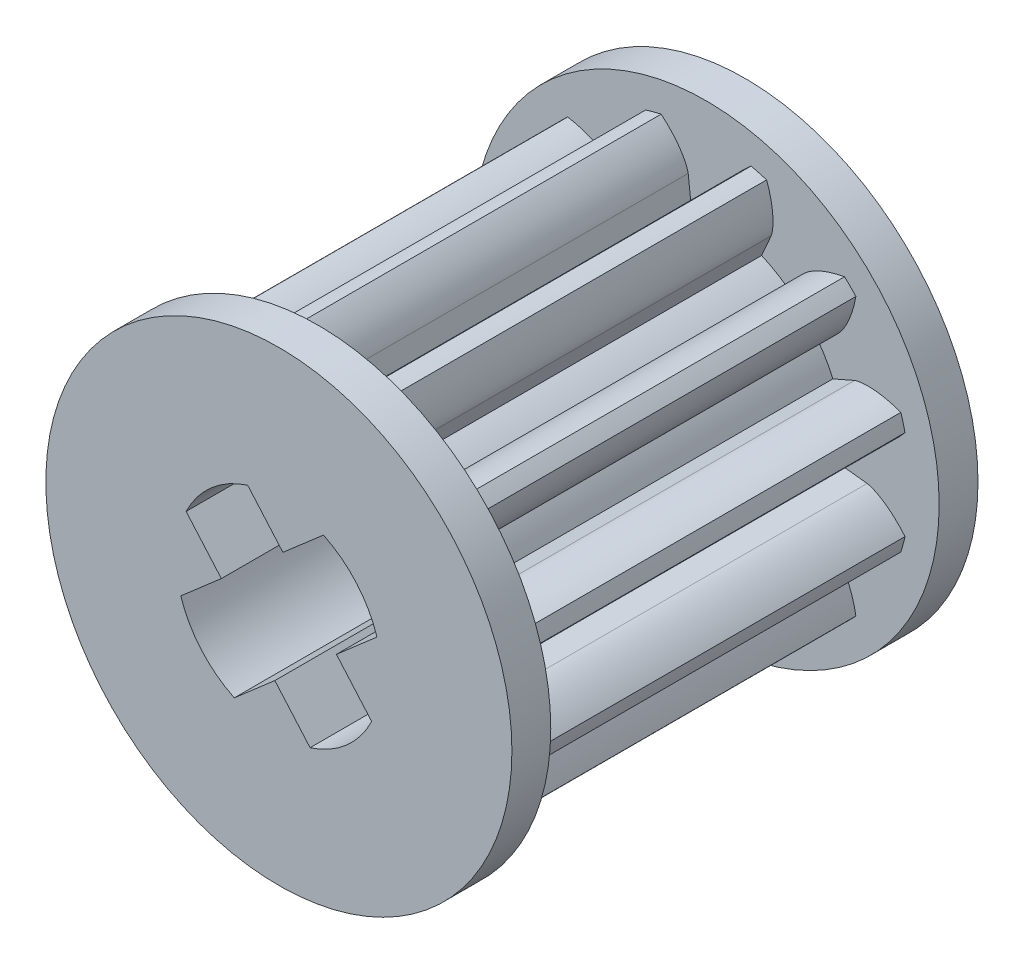
SolidWorks part; units mm, degrees
ref_plane "Front Plane" through (0, 0, 0) normal (0, 0, 1) x (1, 0, 0)
ref_plane "Top Plane" through (0, 0, 0) normal (0, 1, 0) x (1, 0, 0)
ref_plane "Right Plane" through (0, 0, 0) normal (1, 0, 0) x (0, 0, -1)
ref_axis "Axis1" [suppressed] through (0, 0, 71.2135) along (0, 0, -1)
sketch "Sketch1" plane through (0, 0, 0) normal (0, 0, 1) x (1, 0, 0)
  circle A0 centre (0, 0) radius 3.5625
  circle A1 centre (0, 0) radius 4.1723
  circle A2 centre (0, 0) radius 3.75
  circle A3 centre (0, 0) radius 4.5
  circle A4 centre (0, 0) radius 5.25
  dimension "Pitch" = 9
  dimension "Addendum" = 10.5
  dimension "Clearance" = 7.5
  dimension "Base" = 8.3447
  dimension "Root" = 7.125
extrude "Boss-Extrude1" add sketch "Sketch1" along normal blind 10 contours A4
sketch "Sketch3" plane through (0, 0, 0) normal (0, 0, 1) x (1, 0, 0)
  line L0 (0.4615, 4.1467) -> (0, 0) construction
  line L1 (0.7855, 4.0977) -> (0, 0) construction
  line L2 (1.1046, 4.0235) -> (0, 0) construction
  line L3 (1.4168, 3.9244) -> (0, 0) construction
  line L4 (1.7204, 3.8011) -> (0, 0) construction
  line L5 (2.0133, 3.6544) -> (0, 0) construction
  line L6 (2.2938, 3.4852) -> (0, 0) construction
  line L7 (2.5602, 3.2945) -> (0, 0) construction
  line L8 (2.8108, 3.0835) -> (0, 0) construction
  line L9 (3.044, 2.8534) -> (0, 0) construction
  line L10 (3.2585, 2.6058) -> (0, 0) construction
  line L11 (0.7855, 4.0977) -> (0.4636, 4.1594) construction
  line L12 (3.2585, 2.6058) -> (1.2119, 5.1651) construction
  line L13 (1.1046, 4.0235) -> (0.4725, 4.197) construction
  line L14 (1.4168, 3.9244) -> (0.4922, 4.2582) construction
  line L15 (1.7204, 3.8011) -> (0.5262, 4.3416) construction
  line L16 (2.0133, 3.6544) -> (0.5782, 4.4451) construction
  line L17 (2.2938, 3.4852) -> (0.6514, 4.5662) construction
  line L18 (2.5602, 3.2945) -> (0.7489, 4.702) construction
  line L19 (2.8108, 3.0835) -> (0.8734, 4.8495) construction
  line L20 (3.044, 2.8534) -> (1.0271, 5.0051) construction
  line L21 (0, 0) -> (0, 4.5) construction
  line L22 (0, 0) -> (0.5874, 4.4615)
  line L23 (0, 0) -> (-0.5874, 4.4615)
  line L24 (0.4615, 4.1467) -> (0.3941, 3.5406)
  line L25 (-0.4615, 4.1467) -> (-0.3941, 3.5406)
  circle A0 centre (0, 0) radius 4.1723 construction
  circle A1 centre (0, 0) radius 4.5 construction
  arc A2 (3.2585, 2.6058) -> (0.4615, 4.1467) centre (0, 0) ccw construction
  circle A3 centre (0, 0) radius 3.5625 construction
  circle A4 centre (0, 0) radius 3.5625
  circle A5 centre (0, 0) radius 5.25 construction
  circle A6 centre (0, 0) radius 5.25
  spline S0 degree 3 poles (0.4615, 4.1467) (0.464, 4.1637) (0.473, 4.2013) (0.4941, 4.2666) (0.5286, 4.35) (0.6061, 4.5031) (0.722, 4.6743) (0.9298, 4.9199) (1.0915, 5.0686) (1.2119, 5.1651) knots 0 0 0 0 0.040008 0.090018 0.16003 0.250047 0.489907 0.639935 1 1 1 1
  spline S1 degree 3 poles (-0.4615, 4.1467) (-0.464, 4.1637) (-0.473, 4.2013) (-0.4941, 4.2666) (-0.5286, 4.35) (-0.6061, 4.5031) (-0.722, 4.6743) (-0.9298, 4.9199) (-1.0915, 5.0686) (-1.2119, 5.1651) knots 0 0 0 0 0.040008 0.090018 0.16003 0.250047 0.489907 0.639935 1 1 1 1
  point P18 (0, 0)
  dimension "D2" = 45
  dimension "D3" = 0.3277
  dimension "D4" = 3.2769
  dimension "D5" = 0.6554
  dimension "D6" = 0.9831
  dimension "D7" = 1.3108
  dimension "D8" = 1.6385
  dimension "D9" = 1.9662
  dimension "D10" = 2.2939
  dimension "D11" = 2.6216
  dimension "D12" = 2.9492
  dimension "D13" = 15
  dimension "D1" = 11
extrude "Cut-Extrude3" cut sketch "Sketch3" along normal through all contours S1 L25 A4 L24 S0 A6 region at (0, 4.5519, 0)
fillet "Fillet2" [suppressed] radius 0.05
pattern_circular "CirPattern1" count 12 over 360 about axis through (0, 0, 71.2135) along (0, 0, -1) of "Cut-Extrude3", "Fillet2"
ref_plane "Plane2" through (0, 0, 5) normal (0, 0, 1) x (1, 0, 0)
sketch "Sketch6" plane through (0, 0, 10) normal (0, 0, 1) x (1, 0, 0)
  circle A0 centre (0, 0) radius 6
  dimension "D1" = 12
extrude "Boss-Extrude2" add sketch "Sketch6" along normal blind 1
mirror "Mirror1" about plane through (0, 0, 5) normal (0, 0, 1) of "Boss-Extrude2"
sketch "Sketch5" plane through (0, 0, 0) normal (0, 0, 1) x (1, 0, 0)
  line L0 (-0.8803, 2.2327) -> (0.0791, 1.1286) construction
  line L1 (-1.1286, 0.0791) -> (-2.088, 1.1833) construction
  line L2 (-2.2327, -0.8803) -> (-1.1286, 0.0791) construction
  line L3 (-0.0791, -1.1286) -> (-1.1833, -2.088) construction
  line L4 (0.8803, -2.2327) -> (-0.0791, -1.1286) construction
  line L5 (1.1286, -0.0791) -> (2.088, -1.1833) construction
  line L6 (2.2327, 0.8803) -> (1.1286, -0.0791) construction
  line L7 (0.0791, 1.1286) -> (1.1833, 2.088) construction
  line L8 (-0.8803, 2.2327) -> (0.0791, 1.1286)
  line L9 (-1.1286, 0.0791) -> (-2.088, 1.1833)
  line L10 (-2.2327, -0.8803) -> (-1.1286, 0.0791)
  line L11 (-0.0791, -1.1286) -> (-1.1833, -2.088)
  line L12 (0.8803, -2.2327) -> (-0.0791, -1.1286)
  line L13 (1.1286, -0.0791) -> (2.088, -1.1833)
  line L14 (2.2327, 0.8803) -> (1.1286, -0.0791)
  line L15 (0.0791, 1.1286) -> (1.1833, 2.088)
  line L16 (0.1039, 1.4813) -> (1.1479, 2.3885)
  line L17 (-0.8033, 2.5253) -> (0.1039, 1.4813)
  line L18 (-1.4813, 0.1039) -> (-2.3885, 1.1479)
  line L19 (-2.5253, -0.8033) -> (-1.4813, 0.1039)
  line L20 (-0.1039, -1.4813) -> (-1.1479, -2.3885)
  line L21 (0.8033, -2.5253) -> (-0.1039, -1.4813)
  line L22 (1.4813, -0.1039) -> (2.3885, -1.1479)
  line L23 (2.5253, 0.8033) -> (1.4813, -0.1039)
  arc A0 (-0.8803, 2.2327) -> (-2.088, 1.1833) centre (0, 0) ccw construction
  arc A1 (-2.2327, -0.8803) -> (-1.1833, -2.088) centre (0, 0) ccw construction
  arc A2 (0.8803, -2.2327) -> (2.088, -1.1833) centre (0, 0) ccw construction
  arc A3 (2.2327, 0.8803) -> (1.1833, 2.088) centre (0, 0) ccw construction
  arc A4 (-0.8803, 2.2327) -> (-2.088, 1.1833) centre (0, 0) ccw
  arc A5 (-2.2327, -0.8803) -> (-1.1833, -2.088) centre (0, 0) ccw
  arc A6 (0.8803, -2.2327) -> (2.088, -1.1833) centre (0, 0) ccw
  arc A7 (2.2327, 0.8803) -> (1.1833, 2.088) centre (0, 0) ccw
  arc A10 (2.5253, 0.8033) -> (1.1479, 2.3885) centre (0, 0) ccw
  arc A11 (-0.8033, 2.5253) -> (-2.3885, 1.1479) centre (0, 0) ccw
  arc A13 (-2.5253, -0.8033) -> (-1.1479, -2.3885) centre (0, 0) ccw
  arc A14 (0.8033, -2.5253) -> (2.3885, -1.1479) centre (0, 0) ccw
  dimension "D1" = 0.25
extrude "Cut-Extrude4" cut sketch "Sketch5" along normal through all both and the other way through all contours L14 A7 L15 L8 A4 L9 L10 A5 L11 L12 A6 L13 | L21 A14 L22 L23 A10 L16 L17 A11 L18 L19 A13 L20 A7 L14 L13 A6 L12 L11 A5 L10 L9 A4 L8 L15 region at (0, 0, 0) region at (0.6727, 1.881, 0)
equation "\"Module\"= .75"
equation "\"numTeeth\"= 12"
equation "\"pressureAngle\"= 22deg"
equation "\"toothRadius\"= .05"
equation "\"Pitch@Sketch1\"=\"Module\"*\"numTeeth\""
equation "\"Addendum@Sketch1\"=\"Pitch@Sketch1\"+\"Module\"*2"
equation "\"Clearance@Sketch1\"=\"Pitch@Sketch1\"-\"Module\"*2"
equation "\"Base@Sketch1\"=\"Pitch@Sketch1\"*cos(\"pressureAngle\")"
equation "\"Root@Sketch1\"=\"Pitch@Sketch1\"-\"Module\"*1.25*2"
equation "\"D4@Sketch3\"= \"Base@Sketch1\" * pi / 8"
equation "\"D3@Sketch3\"= \"D4@Sketch3\" / 10"
equation "\"D5@Sketch3\"=\"D3@Sketch3\"*2"
equation "\"D6@Sketch3\"=\"D3@Sketch3\"*3"
equation "\"D7@Sketch3\"=\"D3@Sketch3\"*4"
equation "\"D8@Sketch3\"=\"D3@Sketch3\"*5"
equation "\"D9@Sketch3\"=\"D3@Sketch3\"*6"
equation "\"D10@Sketch3\"=\"D3@Sketch3\"*7"
equation "\"D11@Sketch3\"=\"D3@Sketch3\"*8"
equation "\"D12@Sketch3\"=\"D3@Sketch3\"*9"
equation "\"D13@Sketch3\"=180/\"numTeeth\""
equation "\"D1@CirPattern1\"=\"numTeeth\""
equation "\"D1@Fillet2\"= \"toothRadius\""
